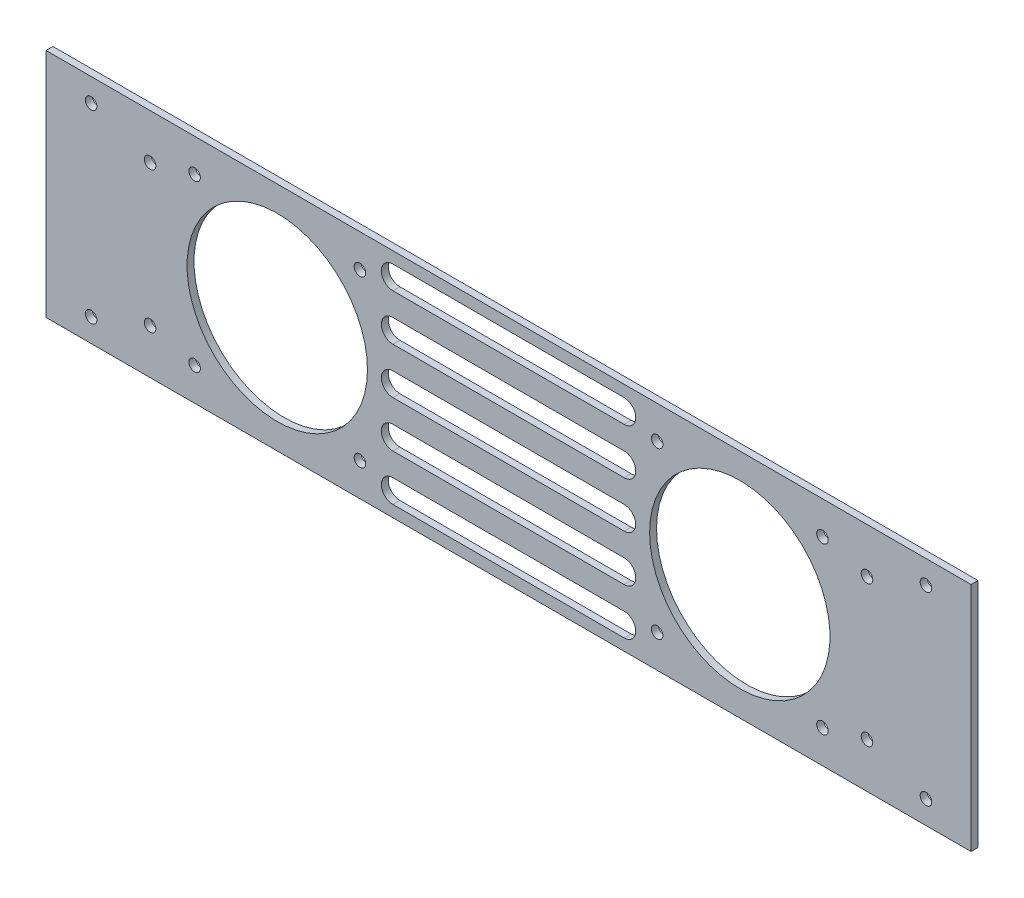
SolidWorks part; units mm, degrees
ref_plane "Front Plane" through (0, 0, 0) normal (0, 0, 1) x (1, 0, 0)
ref_plane "Top Plane" through (0, 0, 0) normal (0, 1, 0) x (1, 0, 0)
ref_plane "Right Plane" through (0, 0, 0) normal (1, 0, 0) x (0, 0, -1)
sketch "Sketch1" plane through (0, 0, 0) normal (0, 0, 1) x (1, 0, 0)
  line L1 (-200, -50) -> (200, -50)
  line L2 (-200, -50) -> (-200, 50)
  line L3 (-200, 50) -> (200, 50)
  line L4 (200, -50) -> (200, 50)
  point P4 (0, 50)
  point P7 (-200, 0)
  dimension "D1" = 100
  dimension "D2" = 400
extrude "Boss-Extrude1" add sketch "Sketch1" along normal blind 3
sketch "Sketch2" plane through (0, 0, 3) normal (0, 0, 1) x (1, 0, 0)
  line L0 (0, -1000) -> (0, 49000) construction
  line L1 (-200, 50) -> (-200, -50) construction
  line L6 (135.75, 35.75) -> (135.75, -35.75) construction
  line L7 (64.25, -35.75) -> (135.75, -35.75) construction
  line L8 (64.25, 35.75) -> (64.25, -35.75) construction
  line L9 (-64.25, 35.75) -> (-135.75, 35.75) construction
  line L10 (-64.25, 35.75) -> (-64.25, -35.75) construction
  line L11 (-64.25, -35.75) -> (-135.75, -35.75) construction
  line L12 (-135.75, 35.75) -> (-135.75, -35.75) construction
  line L13 (64.25, 35.75) -> (135.75, 35.75) construction
  circle A0 centre (-64.25, 35.75) radius 2.5
  circle A1 centre (-64.25, -35.75) radius 2.5
  circle A2 centre (-135.75, -35.75) radius 2.5
  circle A3 centre (-135.75, 35.75) radius 2.5
  circle A4 centre (-100, 0) radius 39
  circle A5 centre (100, 0) radius 39
  circle A6 centre (135.75, 35.75) radius 2.5
  circle A7 centre (135.75, -35.75) radius 2.5
  circle A8 centre (64.25, -35.75) radius 2.5
  circle A9 centre (64.25, 35.75) radius 2.5
  point P1 (-100, 0)
  point P8 (-100, 35.75)
  point P11 (-200, 0)
  point P16 (-135.75, 0)
  dimension "D2" = 5
  dimension "D4" = 78
  dimension "D1" = 100
  dimension "D3" = 71.5
extrude "Cut-Extrude1" cut sketch "Sketch2" against normal through all
sketch "Sketch3" plane through (0, 0, 3) normal (0, 0, 1) x (1, 0, 0)
  line L0 (-1000, 0) -> (49000, 0) construction
  line L1 (0, -1000) -> (0, 49000) construction
  line L2 (-50, 0) -> (50, 0) construction
  line L3 (-50, 5) -> (50, 5)
  line L4 (-50, -5) -> (50, -5)
  line L5 (-50, 20) -> (50, 20) construction
  line L6 (-50, 25) -> (50, 25)
  line L7 (-50, 15) -> (50, 15)
  line L8 (-50, 40) -> (50, 40) construction
  line L9 (-50, 45) -> (50, 45)
  line L10 (-50, 35) -> (50, 35)
  line L11 (-50, 0) -> (-50, 20) construction
  line L12 (-50, -40) -> (50, -40) construction
  line L13 (-50, -45) -> (50, -45)
  line L14 (-50, -35) -> (50, -35)
  line L15 (-50, -20) -> (50, -20) construction
  line L16 (-50, -25) -> (50, -25)
  line L17 (-50, -15) -> (50, -15)
  arc A0 (-50, 5) -> (-50, -5) centre (-50, 0) ccw
  arc A1 (50, -5) -> (50, 5) centre (50, 0) ccw
  arc A2 (-50, 25) -> (-50, 15) centre (-50, 20) ccw
  arc A3 (50, 15) -> (50, 25) centre (50, 20) ccw
  arc A4 (-50, 45) -> (-50, 35) centre (-50, 40) ccw
  arc A5 (50, 35) -> (50, 45) centre (50, 40) ccw
  arc A6 (-50, -45) -> (-50, -35) centre (-50, -40) cw
  arc A7 (50, -35) -> (50, -45) centre (50, -40) cw
  arc A8 (-50, -25) -> (-50, -15) centre (-50, -20) cw
  arc A9 (50, -15) -> (50, -25) centre (50, -20) cw
  point P7 (0, 0)
  point P15 (0, 20)
  point P22 (0, 40)
  point P30 (0, -40)
  point P37 (0, -20)
  dimension "D3" = 5
  dimension "D1" = 100
  dimension "D2" = 3
  dimension "D4" = 20
extrude "Cut-Extrude2" cut sketch "Sketch3" against normal through all
sketch "Sketch4" plane through (0, 0, 3) normal (0, 0, 1) x (1, 0, 0)
  line L0 (-1000, 0) -> (49000, 0) construction
  line L1 (-200, -50) -> (200, -50) construction
  line L2 (-200, 50) -> (-200, -50) construction
  line L3 (0, -1000) -> (0, 49000) construction
  circle A0 centre (-155, -30.5) radius 2.5
  circle A1 centre (-155, 30.5) radius 2.5
  circle A2 centre (155, 30.5) radius 2.5
  circle A3 centre (155, -30.5) radius 2.5
  dimension "D2" = 5
  dimension "D1" = 19.5
  dimension "D3" = 45
extrude "Cut-Extrude3" cut sketch "Sketch4" against normal up to next
sketch "Sketch5" plane through (0, 0, 3) normal (0, 0, 1) x (1, 0, 0)
  line L0 (200, 50) -> (-200, 50) construction
  line L1 (-200, -50) -> (200, -50) construction
  line L2 (-200, 50) -> (-200, -50) construction
  line L3 (0, -1000) -> (0, 49000) construction
  circle A0 centre (-180.5, -40) radius 2.5
  circle A1 centre (-180.5, 40) radius 2.5
  circle A3 centre (180.5, 40) radius 2.5
  circle A4 centre (180.5, -40) radius 2.5
  dimension "D2" = 5
  dimension "D4" = 19.5
  dimension "D1" = 10
  dimension "D3" = 10
extrude "Cut-Extrude4" cut sketch "Sketch5" against normal through all
